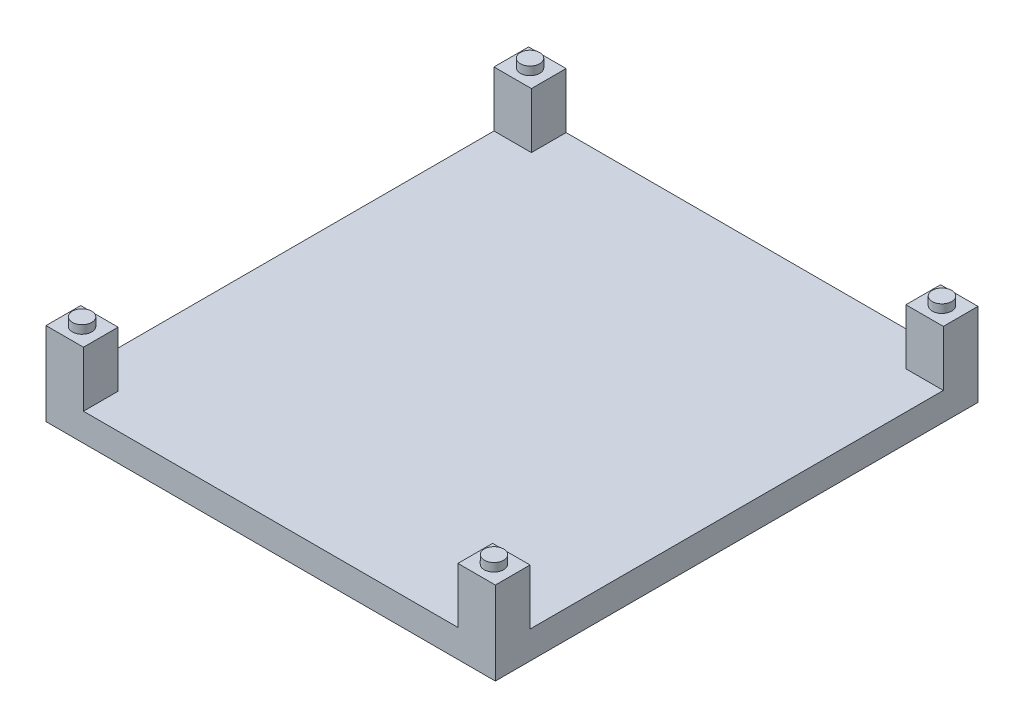
SolidWorks part; units mm, degrees
ref_plane "Front Plane" through (0, 0, 0) normal (0, 0, 1) x (1, 0, 0)
ref_plane "Top Plane" through (0, 0, 0) normal (0, 1, 0) x (1, 0, 0)
ref_plane "Right Plane" through (0, 0, 0) normal (1, 0, 0) x (0, 0, -1)
sketch "Sketch1" plane through (0, 0, 0) normal (0, 1, 0) x (1, 0, 0)
  line L0 (0, -44.45) -> (0, 44.45) construction
  line L1 (-41.275, 44.45) -> (41.275, 44.45)
  line L2 (-41.275, 44.45) -> (-41.275, -44.45)
  line L3 (-41.275, -44.45) -> (41.275, -44.45)
  line L4 (41.275, 44.45) -> (41.275, -44.45)
  line L5 (-41.275, 44.45) -> (41.275, -44.45) construction
  line L6 (-41.275, -44.45) -> (41.275, 44.45) construction
  line L7 (-41.275, 0) -> (41.275, 0) construction
  circle A0 centre (38.1, -41.275) radius 2.3812
  circle A1 centre (-38.1, -41.275) radius 2.3812
  circle A2 centre (38.1, 41.275) radius 2.3812
  circle A3 centre (-38.1, 41.275) radius 2.3812
  point P0 (0, 0)
  dimension "D3" = 76.2
  dimension "D5" = 38.1
  dimension "D6" = 3.175
  dimension "D1" = 88.9
  dimension "D2" = 82.55
  dimension "D4" = 82.55
sketch "Sketch2" plane through (0, 0, 0) normal (0, 1, 0) x (1, 0, 0)
  line L0 (0, -44.196) -> (0, 44.196) construction
  line L1 (-41.148, 44.196) -> (41.148, 44.196)
  line L2 (-41.148, 44.196) -> (-41.148, -44.196)
  line L3 (-41.148, -44.196) -> (41.148, -44.196)
  line L4 (41.148, 44.196) -> (41.148, -44.196)
  line L5 (-41.148, 44.196) -> (41.148, -44.196) construction
  line L6 (-41.148, -44.196) -> (41.148, 44.196) construction
  line L7 (-41.148, 0) -> (41.148, 0) construction
  circle A0 centre (37.719, -41.021) radius 1.778
  circle A1 centre (-37.719, -41.021) radius 1.778
  circle A2 centre (37.719, 41.021) radius 1.778
  circle A3 centre (-37.719, 41.021) radius 1.778
  point P0 (0, 0)
  dimension "D3" = 75.438
  dimension "D5" = 37.719
  dimension "D6" = 3.429
  dimension "D9" = 3.556
  dimension "D10" = 3.556
  dimension "D11" = 3.556
  dimension "D12" = 3.556
  dimension "D1" = 88.392
  dimension "D2" = 82.296
  dimension "D4" = 82.042
  dimension "D13" = 3.429
  dimension "D14" = 3.175
  dimension "D15" = 3.429
  dimension "D16" = 3.175
  dimension "D17" = 3.429
  dimension "D18" = 3.175
extrude "Boss-Extrude2" add sketch "Sketch2" along normal blind 16.764 contours A2 | A3 | A1 | A0
extrude "Boss-Extrude3" add sketch "Sketch2<4>" along normal blind 5.08 contours L2 L1 L4 L3
sketch "Sketch2<4>" plane through (0, 0, 0) normal (0, 1, 0) x (1, 0, 0) same geometry as "Sketch2"
sketch "Sketch4" plane through (0, 0, 0) normal (0, -1, 0) x (1, 0, 0)
  circle A0 centre (-41.148, 44.196) radius 3.2269
  circle A1 centre (41.148, 44.196) radius 3.175
  circle A2 centre (-41.148, -44.196) radius 3.175
  circle A3 centre (41.148, -44.196) radius 3.175
sketch "Sketch5" plane through (0, 5.08, 0) normal (0, 1, 0) x (1, 0, 0)
  line L0 (0, 44.196) -> (0, -44.196) construction
  line L1 (-34.29, 37.846) -> (-41.148, 37.846)
  line L2 (-34.29, 37.846) -> (-34.29, 44.196)
  line L3 (-34.29, 44.196) -> (-41.148, 44.196)
  line L4 (-41.148, 37.846) -> (-41.148, 44.196)
  line L5 (-34.29, 37.846) -> (-41.148, 44.196) construction
  line L6 (-34.29, 44.196) -> (-41.148, 37.846) construction
  line L7 (-41.148, 44.196) -> (41.148, 44.196) construction
  line L12 (-41.148, -44.196) -> (41.148, -44.196) construction
  line L13 (34.29, -44.196) -> (41.148, -44.196)
  line L18 (-34.29, -44.196) -> (-41.148, -37.846) construction
  line L19 (-34.29, -37.846) -> (-41.148, -44.196) construction
  line L20 (-34.29, -44.196) -> (-34.29, -37.846)
  line L21 (-34.29, -44.196) -> (-41.148, -44.196)
  line L22 (-41.148, -44.196) -> (-41.148, -37.846)
  line L23 (-34.29, -37.846) -> (-41.148, -37.846)
  line L24 (41.402, 37.846) -> (41.402, 44.196) [skipped]
  line L25 (41.402, 37.846) -> (34.544, 37.846) [skipped]
  line L26 (34.544, 37.846) -> (34.544, 44.196) [skipped]
  line L27 (41.402, 44.196) -> (34.544, 44.196) [skipped]
  line L28 (41.402, 37.846) -> (34.544, 44.196) construction
  line L29 (41.402, 44.196) -> (34.544, 37.846) construction
  line L30 (41.402, -44.196) -> (41.402, -37.846) [skipped]
  line L31 (41.402, -44.196) -> (34.544, -44.196) [skipped]
  line L32 (34.544, -44.196) -> (34.544, -37.846) [skipped]
  line L33 (41.402, -37.846) -> (34.544, -37.846) [skipped]
  line L34 (41.402, -44.196) -> (34.544, -37.846) construction
  line L35 (41.402, -37.846) -> (34.544, -44.196) construction
  line L36 (41.148, -44.196) -> (41.148, -37.846)
  line L37 (34.29, -37.846) -> (41.148, -37.846)
  line L38 (34.29, -44.196) -> (34.29, -37.846)
  line L39 (34.29, 44.196) -> (41.148, 44.196)
  line L40 (41.148, 37.846) -> (41.148, 44.196)
  line L41 (34.29, 37.846) -> (41.148, 37.846)
  line L42 (34.29, 37.846) -> (34.29, 44.196)
  point P0 (-37.719, 41.021)
  point P5 (37.973, 41.021)
  point P6 (37.973, -41.021)
  point P22 (-37.719, -41.021)
  dimension "D1" = 6.35
  dimension "D2" = 6.858
  dimension "D3" = 2
  dimension "D4" = 2
extrude "Boss-Extrude4" add sketch "Sketch5" along normal blind 10.16
sketch "Sketch3" plane through (0, 21.844, 0) normal (0, 1, 0) x (1, 0, 0)
  line L0 (37.8457, -39.2475) -> (37.8457, -42.7945)
  circle A2 centre (37.719, -41.021) radius 1.778 construction
  arc A3 (37.8457, -39.2475) -> (37.8457, -42.7945) centre (37.9724, -41.021) cw
